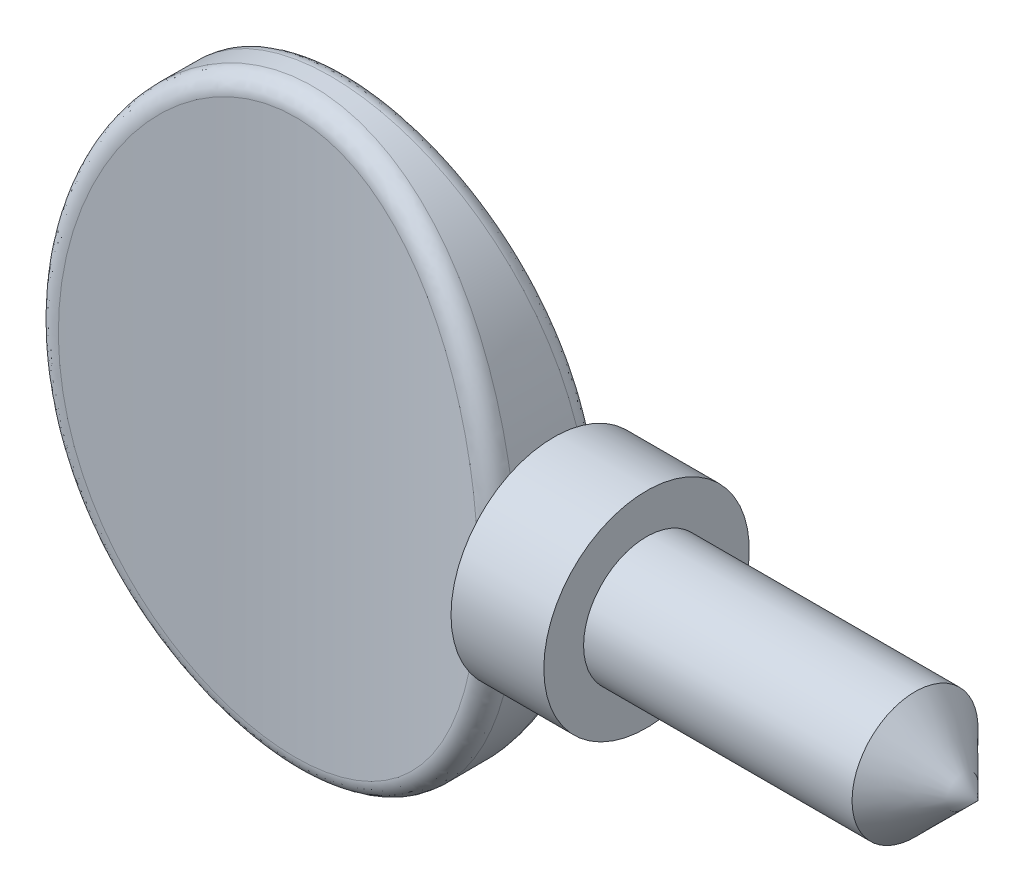
SolidWorks part; units mm, degrees
ref_plane "Front" through (0, 0, 0) normal (0, 0, 1) x (1, 0, 0)
ref_plane "Top" through (0, 0, 0) normal (0, 1, 0) x (1, 0, 0)
ref_plane "Right" through (0, 0, 0) normal (1, 0, 0) x (0, 0, -1)
ref_axis "Axis1" through (-50, 0, 0) along (1, 0, 0)
sketch "Sketch1" plane through (0, 0, 0) normal (0, 0, 1) x (1, 0, 0)
  line L0 (0, 0) -> (25.146, 0) construction
  line L1 (12.446, -3.937) -> (12.446, 3.937)
  ellipse E0 centre (0, 0) end of major axis (0, 11.303) minor radius 8.89
  dimension "D2" = 3.556
extrude "Extrude1" add sketch "Sketch1" along normal mid plane 4.572
sketch "Sketch2" plane through (0, 0, 0) normal (0, 1, 0) x (1, 0, 0)
  line L0 (8.89, 2.286) -> (-8.89, 2.286) construction
  line L1 (0, 0) -> (0, 1.1721) construction
  line L2 (-1.7991, 0) -> (2.0444, 0) construction
  line L3 (-8.89, -2.286) -> (8.89, -2.286) construction
  line L6 (-8.89, 2.286) -> (-8.89, -2.286)
  line L7 (8.89, 2.286) -> (8.89, -2.286)
  arc A0 (-8.89, 2.286) -> (8.89, 2.286) centre (0, 32.766) ccw
  arc A1 (-8.89, -2.286) -> (8.89, -2.286) centre (0, -32.766) cw
extrude "Cut-Extrude1" cut sketch "Sketch2" against normal through all and the other way through all flip side to cut
fillet "Fillet3" radius 0.6773 2 edges at (-8.875, -0.6558, 2.2816) (-1.5369, -11.1328, -1.0532)
sketch "Sketch3" plane through (0, 0, 0) normal (0, 1, 0) x (1, 0, 0)
  line L0 (12.446, 3.937) -> (12.446, 2.413)
  line L1 (0, 0) -> (18.8263, 0) construction
  line L2 (0, 0) -> (25.146, 0) construction
  line L3 (12.446, 2.413) -> (12.446, 0) construction
  line L4 (12.446, 2.413) -> (22.733, 2.413)
  line L5 (22.733, 2.413) -> (25.146, 0)
  line L6 (12.446, 3.937) -> (8.89, 3.937)
  line L7 (7.2364, 1.8517) -> (7.2364, 0)
  line L8 (8.89, 0) -> (8.89, 3.937) construction
  line L9 (7.2364, 0) -> (25.146, 0)
  arc A0 (8.89, 3.937) -> (7.2364, 1.8517) centre (6.7483, 3.937) cw
  arc A3 (-8.89, 2.286) -> (8.89, 2.286) centre (0, 32.766) ccw construction
  dimension "D1" = 7.874
  dimension "D2" = 45
revolve "Revolve1" add sketch "Sketch3" angle 360 about L0
cosmetic thread "Cosmetic Thread1" [suppressed]
sketch "Sketch4" plane through (0, 0, 0) normal (0, 0, 1) x (1, 0, 0)
  line L0 (0, 0) -> (27.7993, 0) construction
  line L1 (22.3341, 2.413) -> (22.733, 1.7221)
  line L2 (22.733, 1.7221) -> (23.1319, 2.413)
  line L3 (23.1319, 2.413) -> (23.1319, 3.2108)
  line L4 (23.1319, 3.2108) -> (22.3341, 3.2108)
  line L5 (22.3341, 3.2108) -> (22.3341, 2.413)
  line L6 (22.733, 2.413) -> (22.733, -2.413) construction
  dimension "D1" = 3.4442
  dimension "D2" = 4.826
revolve "Cut-Revolve10" [suppressed] cut sketch "Sketch4" angle 360 about L0
pattern_linear "LPattern10" [suppressed] count 10 along (-1, 0, 0) of bodies 109
equation "\"D2@Sketch1\" = \"B@Sketch1\" / 6"
equation "\"D1@Sketch3\" = \"E@Sketch1\""
equation "\"D1@Fillet3\" = \"C1@Sketch2\" / 3"
equation "\"D1@Sketch4\" = \"D2@Cosmetic Thread1\""
equation "\"D2@Sketch4\" = \"DIA@Sketch3\""
equation "\"D1@LPattern10\" = (  \"L@Sketch1\"-\"DIA@Sketch3\" / 2 )  / \"P@LPattern10\" "
